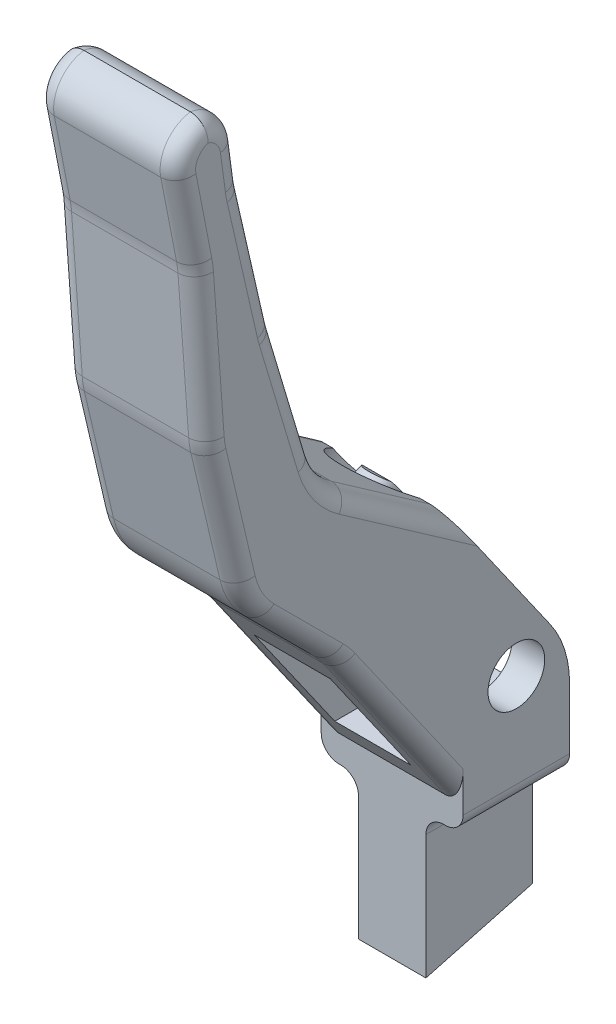
SolidWorks part; units mm, degrees
ref_plane "Front Plane" through (0, 0, 0) normal (0, 0, 1) x (1, 0, 0)
ref_plane "Top Plane" through (0, 0, 0) normal (0, 1, 0) x (1, 0, 0)
ref_plane "Right Plane" through (0, 0, 0) normal (1, 0, 0) x (0, 0, -1)
sketch "Sketch1" plane through (0, 0, 0) normal (1, 0, 0) x (0, 0, -1)
  line L2 (-3, -4.8) -> (-3, -14.3)
  line L3 (-3, -14.3) -> (3, -14.3)
  line L4 (3, 0) -> (3, -14.3)
  line L8 (-3.8829, 9.8298) -> (3, 0)
  line L9 (-3.8829, 9.8298) -> (-10.8457, 14.7052)
  line L10 (-10.8457, 14.7052) -> (-13.5819, 23.8442)
  line L11 (-13.5819, 23.8442) -> (-15.3784, 31.7051)
  line L12 (-15.3784, 31.7051) -> (-15.9196, 35.7422)
  line L13 (-15.9196, 35.7422) -> (-19.51, 35.7422)
  line L15 (-17.4415, 19.459) -> (-15.3784, 10.6458)
  line L16 (-15.3784, 10.6458) -> (-10.1642, 5.4316)
  line L18 (-10.1642, 5.4316) -> (-3, -4.8)
  line L19 (-3.8829, 9.8298) -> (-10.1642, 5.4316) construction
  line L20 (-19.51, 35.7422) -> (-18.0956, 28.5005)
  line L21 (-18.0956, 28.5005) -> (-17.4415, 19.459)
  point P4 (0, -14.3)
  dimension "D1" = 14.3
  dimension "D2" = 6
  dimension "D3" = 9.5
  dimension "D4" = 55
  dimension "D5" = 12
  dimension "D6" = 70
  dimension "D7" = 8.5
  dimension "D8" = 100
extrude "Boss-Extrude1" add sketch "Sketch1" along normal blind 4 and the other way blind 4
sketch "Sketch2" plane through (0, 0, 0) normal (0, 0, 1) x (1, 0, 0)
  line L1 (-2.15, -3.25) -> (2.15, -3.25)
  line L2 (-2.15, -3.25) -> (-2.15, 3.25)
  line L3 (-2.15, 3.25) -> (2.15, 3.25)
  line L4 (2.15, -3.25) -> (2.15, 3.25)
  line L5 (-2.15, -3.25) -> (2.15, 3.25) construction
  line L6 (-2.15, 3.25) -> (2.15, -3.25) construction
  point P0 (0, 0)
  dimension "D1" = 4.3
  dimension "D2" = 6.5
extrude "Cut-Extrude1" cut sketch "Sketch2" against normal through all both and the other way through all
sketch "Sketch3" plane through (0, 0, 0) normal (1, 0, 0) x (0, 0, -1)
  circle A0 centre (0, 0) radius 1.6
  dimension "D1" = 3.2
extrude "Cut-Extrude2" cut sketch "Sketch3" against normal through all both and the other way through all
fillet "Fillet1" radius 6 2 edges at (-3.075, 0, -3) (3.075, 0, -3)
sketch "Sketch4" plane through (0, -14.3, 0) normal (0, -1, 0) x (1, 0, 0)
  line L0 (-4, 3) -> (4, 3) construction
  line L1 (-1.9, -3) -> (1.9, -3)
  line L2 (-1.9, -3) -> (-1.9, 3)
  line L3 (-1.9, 3) -> (1.9, 3)
  line L4 (1.9, -3) -> (1.9, 3)
  line L5 (-1.9, -3) -> (1.9, 3) construction
  line L6 (-1.9, 3) -> (1.9, -3) construction
  point P0 (0, 0)
  line M5 (-4, -3) -> (4, -3)
  line M6 (4, -3) -> (4, 3)
  line M7 (4, 3) -> (-4, 3)
  line M8 (-4, 3) -> (-4, -3)
  dimension "D1" = 3.8
extrude "Cut-Extrude3" cut sketch "Sketch4" against normal blind 8 contours L2 M5 M7 M8 | L4 M5 M6 M7 region at (-2.95, -14.3, 0) region at (2.95, -14.3, 0)
chamfer "Chamfer1" distance 6 angle 15 1 edges at (0, -14.3, -3) first distance on face at (0, -14.3, 0)
ref_plane "Plane1" through (0, 8, 0) normal (0, 1, 0) x (1, 0, 0)
ref_plane "Plane3" through (0, 0, 2.6) normal (0, 0, 1) x (1, 0, 0)
ref_axis "Axis1" through (4.4, 8, 2.6) along (-1, 0, 0)
ref_plane "Plane2" through (0, 0.1002, -0.2753) normal (0, -0.342, 0.9397) x (1, 0, 0)
sketch "Sketch5" plane through (0, 0.1002, -0.2753) normal (0, -0.342, 0.9397) x (1, 0, 0)
  circle A0 centre (0, 10) radius 2.5
  circle A1 centre (0, 10) radius 1
  dimension "D1" = 5
  dimension "D2" = 2
  dimension "D3" = 10
extrude "Cut-Extrude4" cut sketch "Sketch5" against normal up to next and the other way blind 2
fillet "Fillet2" radius 0.5 1 edges at (0, 3.25, -0.7243)
fillet "Fillet4" radius 5 7 edges at (0, 31.7051, 15.3784) (0, 23.8442, 13.5819) (0, 14.7052, 10.8457) (0, 10.6458, 15.3784) (0, 5.4316, 10.1642) (0, 28.5005, 18.0956) (0, 19.459, 17.4415)
fillet "Fillet5" radius 2 2 edges at (0, 35.7422, 15.9196) (0, 35.7422, 19.51)
fillet "Fillet3" radius 1 4 edges at (-1.9, -6.3, 0) (-4, -6.3, 0) (4, -6.3, 0) (1.9, -6.3, 0)
fillet "Fillet6" radius 1 36 edges at (4, 35.1463, 16.2452) (4, 32.9699, 15.548) (4, 31.7061, 15.3733) (4, 27.7439, 14.4732) (4, 23.8449, 13.5793) (4, 20.0278, 12.4393) (4, 14.877, 10.6078) (4, 0.1366, 6.4567) (4, 5.4193, 10.1789) (4, 7.6894, 12.422) (4, 10.7426, 15.2043) (-4, 0.1366, 6.4567) (-4, 5.4193, 10.1789) (-4, 7.6894, 12.422) (-4, 10.7426, 15.2043) (-4, 11.7691, 6.6525) (-4, 14.877, 10.6078) (-4, 20.0278, 12.4393) (-4, 23.8449, 13.5793) (-4, 35.1463, 16.2452) (-4, 32.9699, 15.548) (-4, 31.7061, 15.3733) (4, 11.7691, 6.6525) (4, 15.554, 16.5274) (-4, 15.554, 16.5274) (-4, 27.7439, 14.4732) (4, 31.0779, 18.599) (4, 28.4993, 18.1047) (4, 24.0262, 17.7719) (4, 19.4614, 17.4261) (-4, 31.0779, 18.599) (-4, 28.4993, 18.1047) (-4, 24.0262, 17.7719) (-4, 19.4614, 17.4261) (4, 34.8965, 18.7149) (-4, 34.8965, 18.7149)
